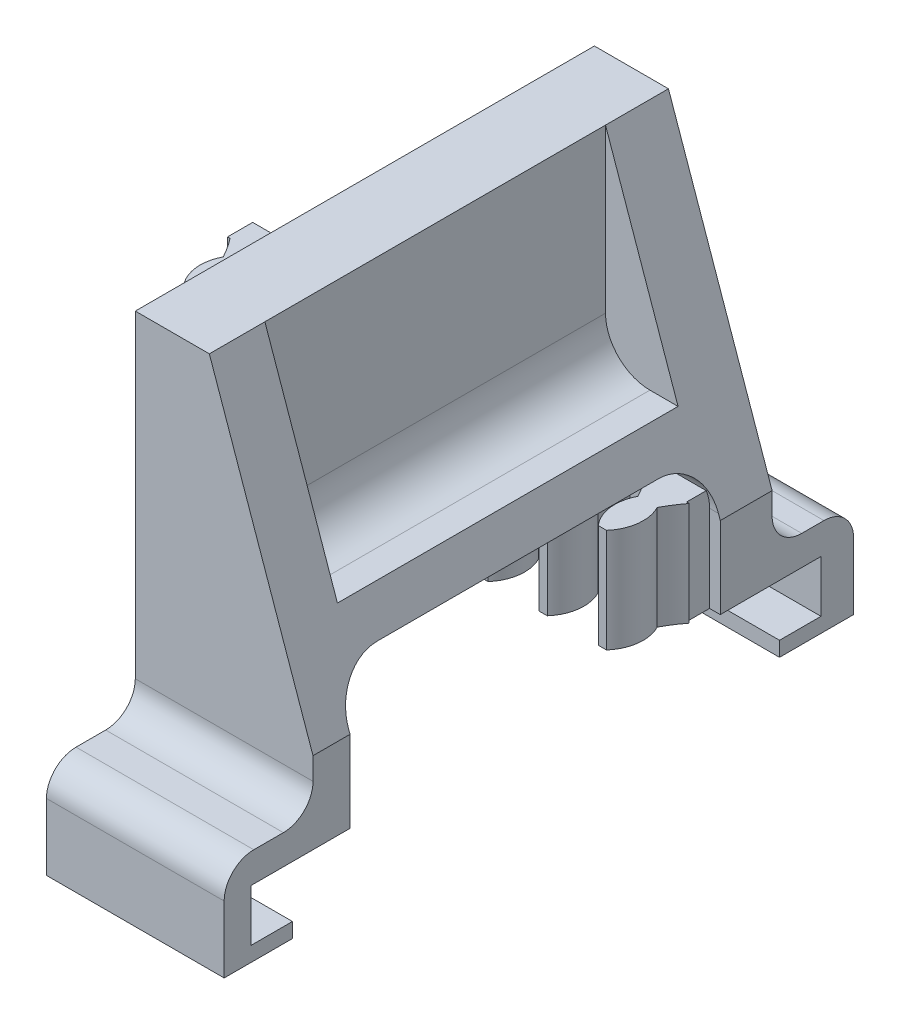
SolidWorks part; units mm, degrees
ref_plane "Front Plane" through (0, 0, 0) normal (0, 0, 1) x (1, 0, 0)
ref_plane "Top Plane" through (0, 0, 0) normal (0, 1, 0) x (1, 0, 0)
ref_plane "Right Plane" through (0, 0, 0) normal (1, 0, 0) x (0, 0, -1)
sketch "Sketch1" plane through (0, 0, 0) normal (0, 0, 1) x (1, 0, 0)
  line L0 (0, 0) -> (0, -30)
  line L1 (0, -30) -> (12, -30)
  line L2 (12, -30) -> (12, -20)
  line L3 (12, -20) -> (5, 0)
  line L4 (5, 0) -> (0, 0)
  dimension "D1" = 30
  dimension "D2" = 12
  dimension "D3" = 10
  dimension "D4" = 5
extrude "Boss-Extrude1" add sketch "Sketch1" against normal blind 31
sketch "Sketch4" plane through (0, 0, 0) normal (-1, 0, 0) x (0, 0, 1)
  line L0 (-31, 0) -> (-31, -30) construction
  line L1 (-27.5, -16.6434) -> (-2.5, -16.6434)
  line L2 (-27.5, -16.6434) -> (-27.5, -31.6434)
  line L3 (-27.5, -31.6434) -> (-2.5, -31.6434)
  line L4 (-2.5, -16.6434) -> (-2.5, -31.6434)
  point P4 (-27.5, -24.1434)
  dimension "D1" = 25
  dimension "D2" = 15
  dimension "D3" = 3.5
extrude "Cut-Extrude2" cut sketch "Sketch4" against normal blind 25 contours L2 L1 L4 L3
ref_plane "Plane1" through (0, 0, -15.25) normal (0, 0, 1) x (1, 0, 0)
sketch "Sketch6" plane through (0, 0, -15.25) normal (0, 0, 1) x (1, 0, 0)
  line L0 (5, 0) -> (5, -14)
  line L1 (5, -14) -> (9.9, -14)
  line L2 (12, -20) -> (5, 0) construction
  line L3 (9.9, -14) -> (5, 0)
  dimension "D1" = 14
extrude "Cut-Extrude4" cut sketch "Sketch6" against normal mid plane 23
ref_plane "Plane3" through (0, -25.5, 0) normal (0, 1, 0) x (1, 0, 0)
sketch "Sketch7" plane through (0, -25.5, 0) normal (0, 1, 0) x (1, 0, 0)
  line L0 (11.2768, 27.65) -> (-19.7232, 27.65)
  line L62 (-16.5, 15.25) -> (16.5, 15.25) construction
  line L162 (11.2768, 27.65) -> (11.2768, 25.95)
  line L172 (-19.7232, 25.95) -> (-19.7232, 27.65)
  line L243 (11.2768, 25.95) -> (-19.7232, 25.95)
  dimension "D2" = 31
  dimension "D3" = 1.7
  dimension "D7" = 12.4
extrude "Boss-Extrude3" add sketch "Sketch7" along normal blind 7
sketch "Sketch10" plane through (0, -25.5, 0) normal (0, 1, 0) x (1, 0, 0)
  line L1 (9.9522, 21.5888) -> (9.9522, 23.4692) construction
  line L2 (10.2298, 21.5888) -> (9.6745, 21.5888)
  line L4 (-19.7232, 25.95) -> (11.2768, 25.95) construction
  line L5 (8.4522, 25.95) -> (11.4522, 25.95)
  arc A0 (10.2298, 21.5888) -> (10.6038, 24.6369) centre (8.1908, 23.386) ccw
  arc A1 (10.6038, 24.6369) -> (11.4522, 25.95) centre (19.0749, 20.0948) cw
  arc A2 (9.3005, 24.6369) -> (8.4522, 25.95) centre (0.8294, 20.0948) ccw
  arc A3 (9.6745, 21.5888) -> (9.3005, 24.6369) centre (11.7135, 23.386) cw
  dimension "D1" = 3
extrude "Boss-Extrude4" add sketch "Sketch10" along normal blind 7
pattern_linear "LPattern1" count 8 spacing 4 along (-1, 0, 0) of "Boss-Extrude4"
sketch "Sketch11" plane through (0, 0, -31) normal (0, 0, -1) x (-1, 0, 0)
  line L0 (-12, -30) -> (-12, -20) construction
  line L1 (-12, -23.5) -> (0, -23.5)
  line L2 (-12, -23.5) -> (-12, -30)
  line L3 (-12, -30) -> (0, -30)
  line L4 (0, -23.5) -> (0, -30)
  dimension "D1" = 6.5
extrude "Boss-Extrude5" add sketch "Sketch11" along normal blind 5.5
fillet "Fillet5" radius 3 3 edges at (5, -14, -15.25) (5.4126, -16.6434, -2.5) (5.4126, -16.6434, -27.5)
sketch "Sketch12" plane through (0, 0, 0) normal (0, 0, 1) x (1, 0, 0)
  line L0 (12, -30) -> (12, -20) construction
  line L1 (0, -30) -> (12, -30)
  line L2 (0, -30) -> (0, -23.5)
  line L3 (0, -23.5) -> (12, -23.5)
  line L4 (12, -30) -> (12, -23.5)
  dimension "D1" = 6.5
extrude "Boss-Extrude6" add sketch "Sketch12" along normal blind 6
sketch "Sketch13" plane through (0, 0, 0) normal (-1, 0, 0) x (0, 0, 1)
  line L0 (-34.3, -25.5) -> (-27.5, -25.5)
  line L1 (-27.5, -25.5) -> (-27.5, -32.0691)
  line L2 (-27.5, -32.0691) -> (-31.5, -32.0691)
  line L3 (-31.5, -32.0691) -> (-31.5, -29)
  line L4 (-31.5, -29) -> (-34.3, -29)
  line L5 (-34.3, -29) -> (-34.3, -25.5)
  line L6 (-15.0561, -22.9316) -> (-15.0561, -37.9805) construction
  line L7 (-2.5, -30) -> (6, -30) construction
  line L9 (-27.5, -25.5) -> (-27.5, -30) construction
  line L12 (1.3878, -29) -> (4.1878, -29)
  line L13 (1.3878, -32.0691) -> (1.3878, -29)
  line L14 (-2.6122, -32.0691) -> (1.3878, -32.0691)
  line L15 (-2.6122, -25.5) -> (-2.6122, -32.0691)
  line L16 (4.1878, -25.5) -> (-2.6122, -25.5)
  line L17 (4.1878, -29) -> (4.1878, -25.5)
  dimension "D1" = 6.8
  dimension "D2" = 0
  dimension "D3" = 4
  dimension "D4" = 3.5
  dimension "D5" = 4.5
extrude "Cut-Extrude5" cut sketch "Sketch13" against normal up to surface (12 mm away) up to face at (12, -24.5, 1.1667)
fillet "Fillet6" radius 2 4 edges at (6, -23.5, -36.5) (6, -23.5, -31) (6, -23.5, 6) (6, -23.5, 0)
